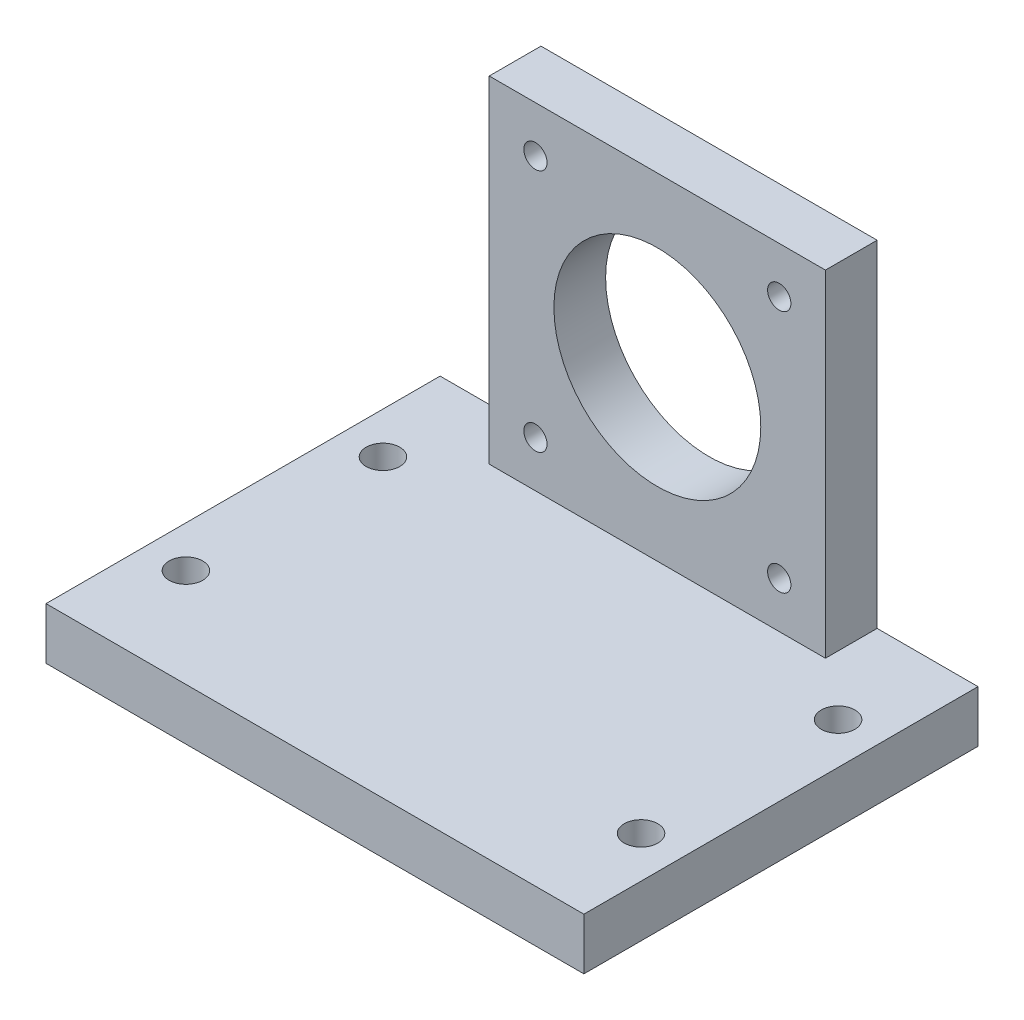
SolidWorks part; units mm, degrees
ref_plane "Front Plane" through (0, 0, 0) normal (0, 0, 1) x (1, 0, 0)
ref_plane "Top Plane" through (0, 0, 0) normal (0, 1, 0) x (1, 0, 0)
ref_plane "Right Plane" through (0, 0, 0) normal (1, 0, 0) x (0, 0, -1)
sketch "Sketch1" plane through (0, 0, 0) normal (0, 0, 1) x (1, 0, 0)
  line L1 (-32.5, 32.5) -> (32.5, 32.5)
  line L2 (-32.5, 32.5) -> (-32.5, -32.5)
  line L3 (-32.5, -32.5) -> (32.5, -32.5)
  line L4 (32.5, 32.5) -> (32.5, -32.5)
  line L5 (-32.5, 32.5) -> (32.5, -32.5) construction
  line L6 (-32.5, -32.5) -> (32.5, 32.5) construction
  circle A0 centre (0, 0) radius 20
  circle A1 centre (23.57, 23.57) radius 2.25
  circle A2 centre (-23.57, 23.57) radius 2.25
  circle A3 centre (-23.57, -23.57) radius 2.25
  circle A4 centre (23.57, -23.57) radius 2.25
  point P0 (0, 0)
  dimension "D1" = 2
  dimension "D2" = 2
extrude "Boss-Extrude1" add sketch "Sketch1" along normal blind 10
sketch "Sketch2" plane through (0, 0, 10) normal (0, 0, 1) x (1, 0, 0)
  line L0 (0, -32.5) -> (-52, -32.5)
  line L1 (-32.5, -32.5) -> (32.5, -32.5) construction
  line L2 (-52, -32.5) -> (-52, -42.5)
  line L3 (-52, -42.5) -> (52, -42.5)
  line L4 (52, -42.5) -> (52, -32.5)
  line L5 (52, -32.5) -> (0, -32.5)
extrude "Boss-Extrude2" add sketch "Sketch2" along normal blind 66.2 and the other way blind 10
sketch "Sketch3" plane through (0, -42.5, 0) normal (0, -1, 0) x (1, 0, 0)
  circle A0 centre (44, 19.05) radius 3.25
  circle A1 centre (-44, 19.05) radius 3.25
  circle A2 centre (-44, 57.15) radius 3.25
  circle A3 centre (44, 57.15) radius 3.25
  dimension "D1" = 2
  dimension "D2" = 2
extrude "Cut-Extrude1" cut sketch "Sketch3" against normal through all
